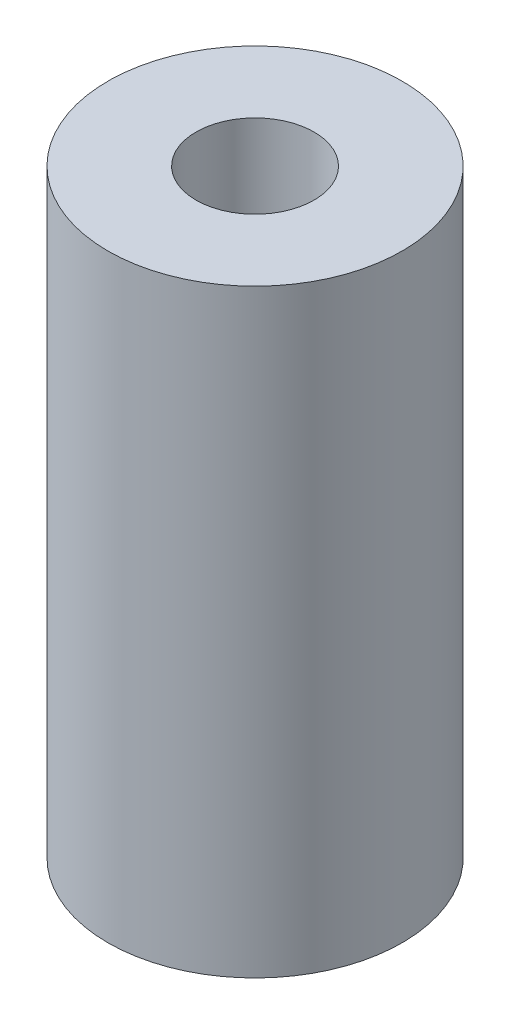
SolidWorks part; units mm, degrees
ref_plane "Front Plane" through (0, 0, 0) normal (0, 0, 1) x (1, 0, 0)
ref_plane "Top Plane" through (0, 0, 0) normal (0, 1, 0) x (1, 0, 0)
ref_plane "Right Plane" through (0, 0, 0) normal (1, 0, 0) x (0, 0, -1)
sketch "Sketch1" plane through (0, 0, 0) normal (0, 1, 0) x (1, 0, 0)
  circle A0 centre (0, 0) radius 3.35
  circle A1 centre (0, 0) radius 8.35
  dimension "D1" = 6.7
  dimension "D2" = 5
extrude "Boss-Extrude1" add sketch "Sketch1" along normal blind 34 contours A1 | A0
ref_plane "Plane1" through (0, 17, 0) normal (0, 1, 0) x (1, 0, 0)
sketch "Sketch2" plane through (0, 17, 0) normal (0, 1, 0) x (1, 0, 0)
  circle A0 centre (0, 0) radius 2.35
  circle A1 centre (0, 0) radius 3.35
  circle A2 centre (0, 0) radius 3.35 construction
  dimension "D1" = 1
extrude "Boss-Extrude2" add sketch "Sketch2" along normal blind 0.5 and the other way blind 0.5
chamfer "Chamfer1" distance 1 angle 45 2 edges at (0, 16.5, 3.35) (0, 17.5, 3.35)
